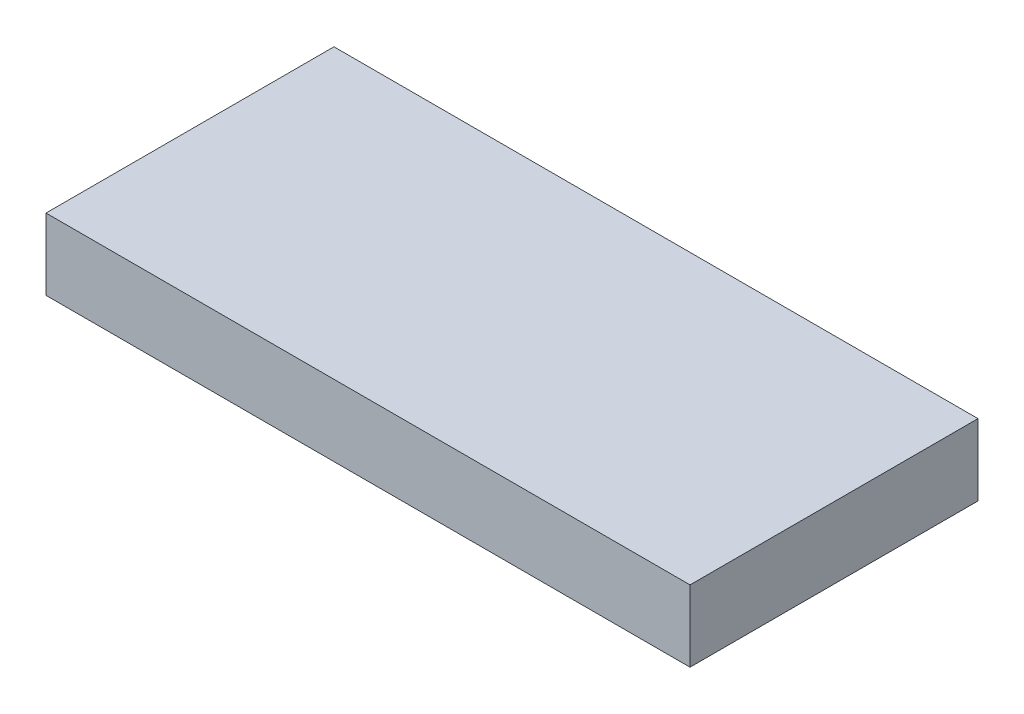
SolidWorks part; units mm, degrees
ref_plane "Front Plane" through (0, 0, 0) normal (0, 0, 1) x (1, 0, 0)
ref_plane "Top Plane" through (0, 0, 0) normal (0, 1, 0) x (1, 0, 0)
ref_plane "Right Plane" through (0, 0, 0) normal (1, 0, 0) x (0, 0, -1)
sketch "Sketch1" plane through (0, 0, 0) normal (0, 1, 0) x (1, 0, 0)
  line L1 (-45.2896, 20.0529) -> (45.0167, 20.0529)
  line L2 (-45.2896, 20.0529) -> (-45.2896, -20.3257)
  line L3 (-45.2896, -20.3257) -> (45.0167, -20.3257)
  line L4 (45.0167, 20.0529) -> (45.0167, -20.3257)
extrude "Boss-Extrude1" add sketch "Sketch1" along normal blind 10
